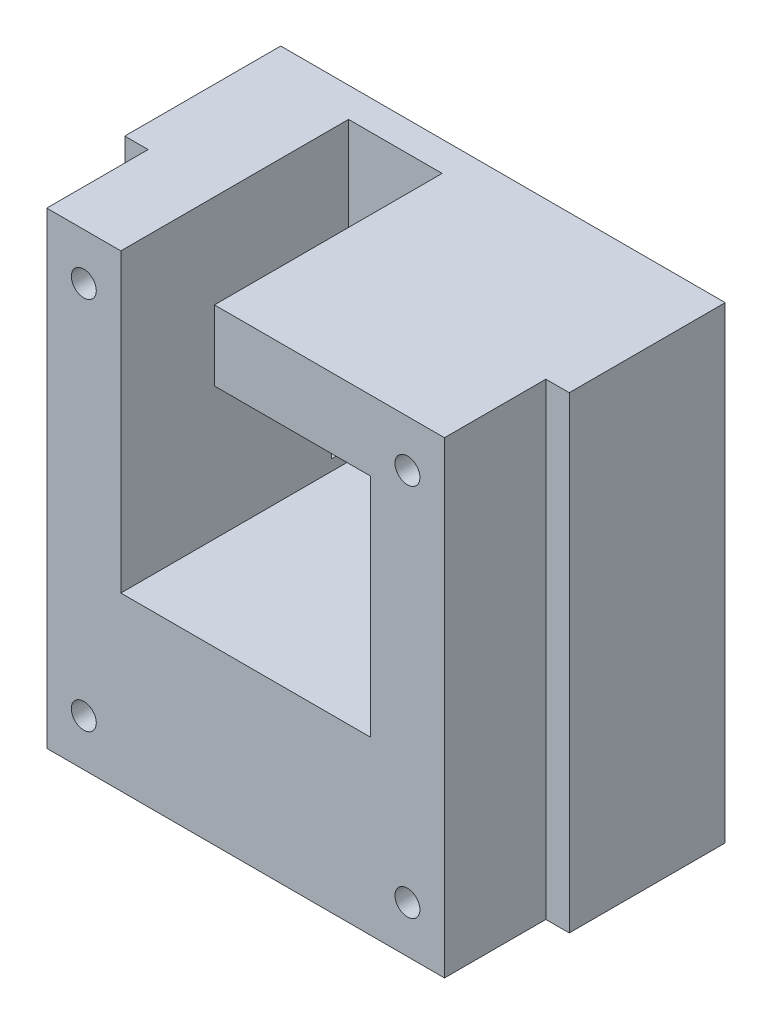
SolidWorks part; units mm, degrees
ref_plane "Front Plane" through (0, 0, 0) normal (0, 0, 1) x (1, 0, 0)
ref_plane "Top Plane" through (0, 0, 0) normal (0, 1, 0) x (1, 0, 0)
ref_plane "Right Plane" through (0, 0, 0) normal (1, 0, 0) x (0, 0, -1)
sketch "Sketch1" plane through (0, 0, 0) normal (0, 0, 1) x (1, 0, 0)
  line L1 (0, 0) -> (28.5, 0)
  line L2 (0, 0) -> (0, 30)
  line L3 (0, 30) -> (28.5, 30)
  line L4 (28.5, 0) -> (28.5, 30)
  dimension "D1" = 28.5
  dimension "D2" = 30
extrude "Boss-Extrude1" add sketch "Sketch1" along normal blind 16.5
sketch "Sketch2" plane through (0, 0, 16.5) normal (0, 0, 1) x (1, 0, 0)
  line L0 (0, 30) -> (0, 0) construction
  line L1 (12.25, 30) -> (12.25, 25.5)
  line L2 (12.25, 25.5) -> (22.25, 25.5)
  line L4 (6.25, 28.4669) -> (6.25, 11)
  line L6 (22.25, 25.5) -> (22.25, 11)
  line L7 (6.25, 28.4669) -> (6.25, 30)
  line L8 (28.5, 30) -> (0, 30) construction
  line L9 (6.25, 30) -> (12.25, 30)
  line L10 (6.25, 11) -> (22.25, 11)
  dimension "D1" = 16
  dimension "D2" = 14.5
  dimension "D3" = 6.25
  dimension "D4" = 6
  dimension "D5" = 4.5
extrude "Cut-Extrude1" cut sketch "Sketch2" against normal blind 14.6
sketch "Sketch3" plane through (0, 0, 1.9) normal (0, 0, 1) x (1, 0, 0)
  line L0 (6.25, 11) -> (22.25, 11) construction
  line L2 (22.25, 11) -> (22.25, 25.5) construction
  circle A0 centre (18.75, 14.5) radius 2.8
  dimension "D2" = 3.5
  dimension "D3" = 5.6
  dimension "D1" = 3.5
extrude "Cut-Extrude2" cut sketch "Sketch3" against normal through all
sketch "Sketch4" plane through (0, 0, 0) normal (0, 0, -1) x (-1, 0, 0)
  line L5 (-18.75, 17.3) -> (0, 17.3)
  line L9 (0, 30) -> (0, 0) construction
  line L10 (0, 11.7) -> (-18.75, 11.7)
  line L11 (0, 17.3) -> (0, 11.7)
  circle A2 centre (-18.75, 14.5) radius 2.8 construction
  arc A3 (-18.75, 11.7) -> (-18.75, 17.3) centre (-18.75, 14.5) cw
extrude "Cut-Extrude3" cut sketch "Sketch4" against normal blind 3
sketch "Sketch5" plane through (0, 0, 0) normal (0, 0, 1) x (1, 0, 0)
  line L0 (28.5, 30) -> (12.25, 30) construction
  line L1 (28.5, 0) -> (28.5, 30) construction
  line L2 (0, 15) -> (28.5, 15) construction
  line L3 (0, 30) -> (0, 0) construction
  line L4 (14.25, 0) -> (14.25, 30) construction
  line L5 (0, 0) -> (28.5, 0) construction
  line L8 (6.25, 30) -> (0, 30) construction
  circle A0 centre (24.625, 27) radius 0.8
  circle A1 centre (24.625, 3) radius 0.8
  circle A2 centre (3.875, 3) radius 0.8
  circle A3 centre (3.875, 27) radius 0.8
  point P14 (14.25, 15)
  point P24 (14.25, 15)
  dimension "D1" = 1.6
  dimension "D4" = 3
  dimension "D6" = 3
  dimension "D2" = 3
  dimension "D3" = 3.875
  dimension "D5" = 3.875
sketch "Sketch6" [suppressed] plane through (0, 0, 16.5) normal (0, 0, 1) x (1, 0, 0)
  line L0 (22.25, 25.5) -> (6.25, 11) construction
  line L1 (22.25, 11) -> (6.25, 25.5) construction
  line L2 (6.25, 30) -> (6.25, 11) construction
  circle A1 centre (14.25, 18.25) radius 2.8553
  point P9 (14.25, 18.25)
sketch "Sketch7" plane through (0, 0, 16.5) normal (0, 0, 1) x (1, 0, 0)
  line L0 (0, 0) -> (28.5, 0) construction
  line L1 (0, 30) -> (1.5, 30)
  line L2 (0, 30) -> (0, 0)
  line L3 (0, 0) -> (1.5, 0)
  line L4 (1.5, 30) -> (1.5, 0)
  line L6 (28.5, 30) -> (27, 30)
  line L7 (28.5, 30) -> (28.5, 0)
  line L8 (28.5, 0) -> (27, 0)
  line L9 (27, 30) -> (27, 0)
  dimension "D1" = 1.5
  dimension "D2" = 1.5
extrude "Cut-Extrude5" cut sketch "Sketch7" against normal blind 6.5
extrude "Cut-Extrude6" cut sketch "Sketch5" against normal blind 6.5 from surface starting at face at (13.85, 19.3, 16.5)
